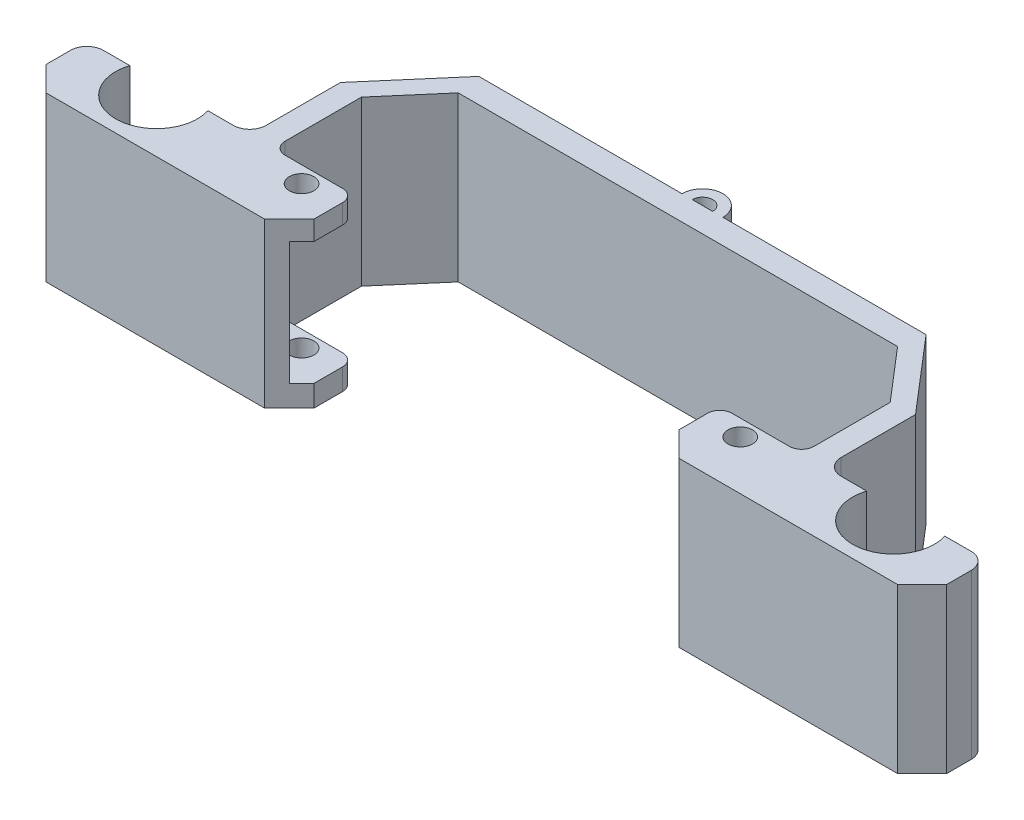
SolidWorks part; units mm, degrees
ref_plane "Front Plane" through (0, 0, 0) normal (0, 0, 1) x (1, 0, 0)
ref_plane "Top Plane" through (0, 0, 0) normal (0, 1, 0) x (1, 0, 0)
ref_plane "Right Plane" through (0, 0, 0) normal (1, 0, 0) x (0, 0, -1)
other "Configuration Table"
sketch "草图1" plane through (0, 0, 0) normal (0, 1, 0) x (1, 0, 0)
  line L0 (-52.3848, 0) -> (-49.7697, 0)
  line L1 (-55, 0) -> (-55, -8)
  line L2 (-55, -8) -> (-32.2872, -8)
  line L3 (55, -8) -> (55, 0)
  line L4 (-40.2303, 0) -> (-35.1152, 0)
  line L5 (49.7697, 0) -> (52.3848, 0)
  line L6 (0, 0) -> (0, 40.3949) construction
  line L7 (-2.25, 24) -> (2.25, 24) construction
  line L10 (-7.25, 24) -> (-2.25, 24)
  line L12 (7.25, 24) -> (2.25, 24)
  line L14 (35.1152, 0) -> (40.2303, 0)
  line L17 (32.2872, -8) -> (55, -8)
  line L28 (-52.3848, 0) -> (-55, 0)
  line L29 (52.3848, 0) -> (55, 0)
  line L30 (-35.1152, 0) -> (-35.1152, 11.0784)
  line L31 (-27.3102, 20.171) -> (27.3102, 20.171)
  line L32 (35.1152, 11.0784) -> (35.1152, 0)
  line L33 (-32.2872, -8) -> (-32.2872, 10.8118)
  line L34 (-26.8285, 17.171) -> (26.8285, 17.171)
  line L35 (32.2872, 10.8118) -> (32.2872, -8)
  line L36 (-32.2872, 10.8118) -> (-26.8285, 17.171)
  line L37 (-35.1152, 11.0784) -> (-27.3102, 20.171)
  line L38 (32.2872, 10.8118) -> (26.8285, 17.171)
  line L39 (35.1152, 11.0784) -> (27.3102, 20.171)
  arc A0 (-49.7697, 0) -> (-40.2303, 0) centre (-45, -1.5) ccw
  arc A1 (40.2303, 0) -> (49.7697, 0) centre (45, -1.5) ccw
  point P4 (0, 0)
  point P14 (0, 24)
  dimension "D4" = 10
  dimension "D1" = 110
  dimension "D2" = 1.5
  dimension "D3" = 45
  dimension "D5" = 8
  dimension "D6" = 90
  dimension "D7" = 10
  dimension "D8" = 4.5
  dimension "D9" = 3
  dimension "D12" = 24
extrude "凸台-拉伸1" add sketch "草图1" along normal blind 20 contours A1 L14 L32 L31 L30 L4 A0 L0 L28 L1 L2 L33 L34 L35 L17 L3 L29 L5 region at (-51.0773, 0, 1.1355)
sketch "草图2" plane through (0, 20, 0) normal (0, 1, 0) x (1, 0, 0)
  line L1 (-32.2872, -8) -> (-22.2872, -8)
  line L2 (-32.2872, -8) -> (-32.2872, 0)
  line L3 (-32.2872, 0) -> (-22.2872, 0)
  line L4 (-22.2872, -8) -> (-22.2872, 0)
  circle A0 centre (-26.7872, -2) radius 1.5
  point P7 (0, 0)
  dimension "D3" = 3
  dimension "D1" = 8
  dimension "D2" = 10
  dimension "D4" = 5.5
  dimension "D5" = 2
extrude "凸台-拉伸2" add sketch "草图2" against normal up to surface (20 mm away) up to face at (0, 0, -3.6732)
sketch "草图3" plane through (0, 0, 0) normal (0, 0, -1) x (-1, 0, 0)
  line L1 (32.2872, 17.622) -> (22.2872, 17.622)
  line L2 (32.2872, 17.622) -> (32.2872, 2.622)
  line L3 (32.2872, 2.622) -> (22.2872, 2.622)
  line L4 (22.2872, 0) -> (32.2872, 0)
  line L5 (32.2872, 0) -> (32.2872, 20)
  line L6 (32.2872, 20) -> (22.2872, 20)
  line L7 (22.2872, 20) -> (22.2872, 0)
  line L9 (32.2872, 2.622) -> (32.2872, 17.622)
  line L11 (22.2872, 17.622) -> (22.2872, 2.622)
  point P8 (0, 0)
  point P11 (0, 0)
  line M8 (32.2872, 0) -> (32.2872, 20)
  line M10 (22.2872, 20) -> (22.2872, 0)
  dimension "D2" = 15
  dimension "D1" = 0
extrude "切除-拉伸1" cut sketch "草图3" against normal blind 6.5 contours L3 L1 M8 M10 region at (-27.2872, 10.122, 0)
ref_plane "基准面1" through (0, 0, 0) normal (-1, 0, 0) x (0, 0, 1)
mirror "镜向1" about plane through (0, 0, 0) normal (-1, 0, 0) of bodies 103
chamfer "倒角1" distance 3 angle 45 4 edges at (22.2872, 10, 8) (55, 10, 8) (-22.2872, 10, 8) (-55, 10, 8)
fillet "圆角1" radius 2 6 edges at (-35.1152, 10, 0) (35.1152, 10, 0) (55, 10, 0) (32.2872, 10.122, 6.5) (-32.2872, 10.122, 6.5) (-55, 10, 0)
fillet "圆角2" radius 1.5 8 edges at (-22.2872, 1.311, 0) (-22.2872, 18.811, 0) (22.2872, 1.311, 0) (22.2872, 18.811, 0) (32.2872, 18.811, 0) (32.2872, 1.311, 0) (-32.2872, 1.311, 0) (-32.2872, 18.811, 0)
sketch "草图4" plane through (0, 20, 0) normal (0, 1, 0) x (1, 0, 0)
  line L0 (-27.3102, 20.171) -> (27.3102, 20.171) construction
  line L1 (-2.5, 20.171) -> (-1.25, 20.171)
  line L2 (1.25, 20.171) -> (2.5, 20.171)
  arc A0 (1.25, 20.171) -> (-1.25, 20.171) centre (0, 20.171) ccw
  arc A1 (2.5, 20.171) -> (-2.5, 20.171) centre (0, 20.171) ccw
  dimension "D1" = 2.5
  dimension "D2" = 5
extrude "凸台-拉伸3" add sketch "草图4" against normal up to surface (20 mm away) up to face at (0, 0, -1.4851)
